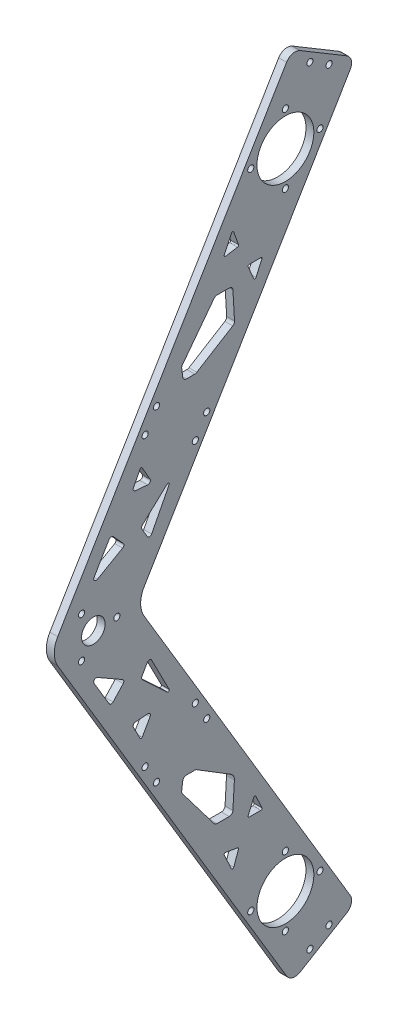
SolidWorks part; units mm, degrees
ref_plane "Front Plane" through (0, 0, 0) normal (1, 0, 0) x (0, 1, 0)
ref_plane "Top Plane" through (0, 0, 0) normal (0, 0, 1) x (0, 1, 0)
ref_plane "Right Plane" through (0, 0, 0) normal (0, 1, 0) x (-1, 0, 0)
sketch "sketch" plane through (0, 0, 0) normal (1, 0, 0) x (0, 1, 0)
  line L0 (260, 0) -> (-260, 0) construction
  line L1 (0, 0) -> (0, 280) construction
  line L2 (0, 280) -> (0, 197.29) construction
  line L3 (0, 197.29) -> (260, 0) construction
  line L4 (0, 197.29) -> (-260, 0) construction
  line L5 (0, 0) -> (130, 98.645) construction
  line L6 (130, 98.645) -> (130, 119.61) construction
  line L7 (130, 98.645) -> (130, 77.68) construction
  line L8 (130, 77.68) -> (0, 0) construction
  line L9 (130, 77.68) -> (260, 0) construction
  circle A0 centre (0, 0) radius 65 construction
  circle A1 centre (260, 0) radius 65 construction
  circle A2 centre (-260, 0) radius 65 construction
  point P4 (0, 0)
  dimension "D1" = 130
  dimension "D2" = 130
  dimension "D4" = 130
  dimension "D5" = 280
  dimension "D3" = 260
  dimension "D6" = 82.71
  dimension "D7" = 20.965
  dimension "D8" = 20.965
sketch "bogie base" plane through (0, 0, 0) normal (1, 0, 0) x (0, 1, 0)
  line L1 (260, 0) -> (-260, 0) construction
  line L3 (-25.7527, -15.3882) -> (9.8719, 5.8988) construction
  line L9 (-31.3951, -5.9456) -> (-20.1104, -24.8309)
  line L15 (285.7527, -15.3882) -> (234.2473, 15.3882) construction
  line L16 (130, 77.68) -> (260, 0) construction
  line L17 (291.3951, -5.9456) -> (280.1104, -24.8309)
  line L25 (124.8706, 92.0889) -> (-30.0131, -0.4601)
  line L26 (124.8706, 57.1411) -> (-14.6249, -26.2128)
  line L27 (135.1294, 57.1411) -> (274.6249, -26.2128)
  line L28 (135.1294, 92.0889) -> (290.0131, -0.4601)
  circle A0 centre (260, 0) radius 11.5 construction
  circle A1 centre (0, 0) radius 11.5 construction
  arc A2 (124.8706, 57.1411) -> (135.1294, 57.1411) centre (130, 48.5569) cw
  arc A3 (124.8706, 92.0889) -> (135.1294, 92.0889) centre (130, 83.5046) cw
  arc A4 (291.3951, -5.9456) -> (290.0131, -0.4601) centre (287.9614, -3.8938) ccw
  arc A5 (280.1104, -24.8309) -> (274.6249, -26.2128) centre (276.6767, -22.7791) cw
  arc A6 (-14.6249, -26.2128) -> (-20.1104, -24.8309) centre (-16.6767, -22.7791) cw
  arc A7 (-31.3951, -5.9456) -> (-30.0131, -0.4601) centre (-27.9614, -3.8938) cw
  point P4 (130, 98.645)
  point P12 (0, 0)
  point P14 (-25.7527, -15.3882)
  point P18 (260, 0)
  point P19 (0, 0)
  point P24 (130, 98.645)
  point P26 (260, 0)
  point P29 (285.7527, -15.3882)
  point P33 (130, 60.2061)
  point P35 (130, 77.68)
  point P37 (130, 95.1539)
  point P38 (130, 77.68)
  point P41 (130, 98.645)
  point P43 (293.4468, -2.5119)
  point P46 (278.0586, -28.2646)
  point P49 (-18.0586, -28.2646)
  point P52 (-33.4468, -2.5119)
  dimension "D11" = 23
  dimension "D12" = 118.28
  dimension "D2" = 23
  dimension "D14" = 10
  dimension "D15" = 10
  dimension "D16" = 4
  dimension "D3" = 90
  dimension "D4" = 30
  dimension "D5" = 30
  dimension "D6" = 90
  dimension "D7" = 30
  dimension "D8" = 30
  dimension "D9" = 190.4034
  dimension "D10" = 34.9478
  dimension "D13" = 241.72
extrude "extrude-base" add sketch "bogie base" along normal blind 3.18
sketch "Sketch4" plane through (0, 0, 0) normal (1, 0, 0) x (0, 1, 0)
  circle A0 centre (260, 0) radius 11.5
  circle A1 centre (0, 0) radius 11.5
  dimension "D1" = 23
  dimension "D2" = 23
extrude "Cut-motor holes\\" cut sketch "Sketch4" along normal blind 3.18
sketch "Sketch5" plane through (0, 0, 0) normal (1, 0, 0) x (0, 1, 0)
  line L0 (0, 15.25) -> (0, -15.25) construction
  line L4 (24.7016, 0) -> (-24.7016, 0) construction
  line L5 (0, 11.5) -> (0, 14) construction
  line L6 (8.1317, 8.1317) -> (-8.1317, -8.1317) construction
  line L8 (251.8683, 8.1317) -> (268.1317, -8.1317) construction
  line L9 (260, 11.5) -> (260, 14) construction
  line L10 (235.2984, 0) -> (284.7016, 0) construction
  circle A0 centre (0, 0) radius 11.5 construction
  circle A1 centre (0, 14) radius 1.25
  circle A2 centre (0, -14) radius 1.25
  circle A3 centre (14, 0) radius 1.25
  circle A4 centre (-14, 0) radius 1.25
  circle A5 centre (260, 0) radius 11.5 construction
  circle A6 centre (274, 0) radius 1.25
  circle A7 centre (246, 0) radius 1.25
  circle A8 centre (260, -14) radius 1.25
  circle A9 centre (260, 14) radius 1.25
  point P13 (0, 0)
  point P22 (0, 0)
  point P45 (260, 0)
  point P46 (260, 0)
  dimension "D1" = 2.5
  dimension "D2" = 14
extrude "motor support holes" cut sketch "Sketch5" along normal blind 3.18
sketch "Sketch6" plane through (0, 0, 0) normal (1, 0, 0) x (0, 1, 0)
  line L0 (130, 82.445) -> (130, 66.92) construction
  line L2 (-25.7527, -15.3882) -> (-23.0229, -13.7571) construction
  line L3 (-25.7527, -15.3882) -> (9.8719, 5.8988) construction
  line L5 (-30.717, -0.8807) -> (-15.3288, -26.6334) construction
  line L6 (124.8706, 57.1411) -> (-14.6249, -26.2128) construction
  line L7 (-25.3312, -9.8942) -> (-20.7147, -17.62) construction
  line L9 (-31.3951, -5.9456) -> (-20.1104, -24.8309) construction
  line L10 (106.8543, 81.3234) -> (122.2425, 55.5707) construction
  line L12 (-23.0229, -13.7571) -> (18.1814, 10.8641) construction
  line L13 (130, 77.68) -> (0, 0) construction
  line L14 (130, 77.68) -> (18.1814, 10.8641) construction
  line L15 (66.3966, 57.1484) -> (81.7848, 31.3957) construction
  line L16 (10.4873, 23.7405) -> (25.8755, -2.0123) construction
  line L17 (77.9536, 46.5803) -> (70.2278, 41.9638) construction
  line L18 (62.5337, 54.8402) -> (77.9219, 29.0875) construction
  line L19 (70.2595, 59.4566) -> (85.6477, 33.7039) construction
  line L20 (62.5337, 54.8402) -> (64.1648, 52.1104) construction
  line L21 (130, 77.68) -> (130, 68.17) construction
  line L22 (130, 68.17) -> (121.7723, 82.4492) construction
  line L23 (121.7723, 82.4492) -> (138.2488, 82.437) construction
  line L24 (138.2488, 82.437) -> (130, 68.17) construction
  line L25 (130, 77.68) -> (121.7723, 82.4492) construction
  circle A17 centre (-25.3312, -9.8942) radius 1.25
  circle A18 centre (-20.7147, -17.62) radius 1.25
  circle A19 centre (64.1648, 52.1104) radius 1.25
  circle A20 centre (71.8906, 56.7269) radius 1.25
  circle A21 centre (76.2908, 31.8172) radius 1.25
  circle A22 centre (84.0166, 36.4337) radius 1.25
  circle A23 centre (130, 77.68) radius 4.765
  circle A24 centre (130, 68.17) radius 1.25
  circle A25 centre (121.7723, 82.4492) radius 1.25
  circle A26 centre (138.2488, 82.437) radius 1.25
  circle A27 centre (175.9834, 36.4337) radius 1.25
  circle A28 centre (183.7092, 31.8172) radius 1.25
  circle A29 centre (195.8352, 52.1104) radius 1.25
  circle A30 centre (188.1094, 56.7269) radius 1.25
  circle A31 centre (280.7147, -17.62) radius 1.25
  circle A32 centre (285.3312, -9.8942) radius 1.25
  point P12 (-23.0229, -13.7571)
  point P15 (-23.0229, -13.7571)
  point P25 (114.5484, 68.4471)
  point P32 (74.0907, 44.272)
  point P35 (18.1814, 10.8641)
  point P38 (74.0907, 44.272)
  point P41 (70.2278, 41.9638)
  point P44 (77.9536, 46.5803)
  dimension "D4" = 2.5
  dimension "D5" = 18
  dimension "D8" = 48
  dimension "D9" = 30
  dimension "D10" = 4.5
  dimension "D1" = 3.18
  dimension "D2" = 2.5
  dimension "D3" = 9
  dimension "D11" = 2.5
  dimension "D13" = 9.53
  dimension "D14" = 2.5
  dimension "D20" = 2.5
  dimension "D21" = 2.5
  dimension "D22" = 19.6131
  dimension "D6" = 30
  dimension "D7" = 30.86
  dimension "D12" = 3.18
  dimension "D15" = 9.51
  dimension "D16" = 16.48
  dimension "D17" = 16.4764
  dimension "D18" = 16.48
  dimension "D19" = 9.51
extrude "support holes" cut sketch "Sketch6" along normal blind 3.18
sketch "Sketch7" plane through (0, 0, 0) normal (1, 0, 0) x (0, 1, 0)
  line L0 (111.4204, 77.3885) -> (101.2093, 71.287)
  line L1 (101.0405, 69.697) -> (105.4282, 65.6076)
  line L2 (106.9782, 65.843) -> (112.8016, 76.034)
  line L3 (107.9696, 55.8657) -> (104.1511, 58.0477)
  line L4 (102.9234, 57.8613) -> (93.556, 47.8105)
  line L5 (94.1503, 47.0249) -> (107.9306, 54.1081)
  line L6 (88.0497, 61.4547) -> (82.8599, 58.7871)
  line L7 (82.8404, 57.9083) -> (88.3944, 54.7346)
  line L8 (130, 77.68) -> (0, 0) construction
  line L9 (89.8876, 55.6799) -> (89.5039, 60.6424)
  line L10 (54.884, 41.6464) -> (38.0344, 28.8608)
  line L11 (0, 0) -> (130, 98.645) construction
  line L12 (37.4411, 27.6659) -> (37.4411, 22.7346)
  line L13 (38.8533, 21.2372) -> (49.1659, 20.6321)
  line L14 (51.8962, 22.054) -> (60.3984, 35.8618)
  line L15 (60.6211, 36.6482) -> (60.6211, 40.0362)
  line L16 (59.3068, 41.5246) -> (55.9763, 41.9399)
  line L17 (24.8845, 24.7214) -> (18.7051, 21.8314)
  line L18 (18.7465, 20.9084) -> (24.1386, 18.9527)
  line L19 (24.8026, 19.3426) -> (25.5899, 24.1883)
  line L20 (39.1024, 11.9231) -> (33.9164, 9.4977)
  line L21 (33.2046, 9.9506) -> (33.2046, 14.5862)
  line L22 (33.9006, 15.0462) -> (39.0866, 12.836)
  line L23 (130, 93.5046) -> (130, 58.5569) construction
  line L24 (226.0994, 15.0462) -> (220.9134, 12.836)
  line L25 (226.7954, 9.9506) -> (226.7954, 14.5862)
  line L26 (220.8976, 11.9231) -> (226.0836, 9.4977)
  line L27 (235.1974, 19.3426) -> (234.4101, 24.1883)
  line L28 (241.2535, 20.9084) -> (235.8614, 18.9527)
  line L29 (235.1155, 24.7214) -> (241.2949, 21.8314)
  line L30 (200.6932, 41.5246) -> (204.0237, 41.9399)
  line L31 (199.3789, 36.6482) -> (199.3789, 40.0362)
  line L32 (208.5739, 21.2905) -> (199.6016, 35.8618)
  line L33 (221.1467, 21.2372) -> (209.939, 20.5796)
  line L34 (222.5589, 27.6659) -> (222.5589, 22.7346)
  line L35 (205.116, 41.6464) -> (221.9656, 28.8608)
  line L36 (170.1124, 55.6799) -> (170.4961, 60.6424)
  line L37 (177.1596, 57.9083) -> (171.6056, 54.7346)
  line L38 (171.9503, 61.4547) -> (177.1401, 58.7871)
  line L39 (165.8497, 47.0249) -> (152.0694, 54.1081)
  line L40 (157.0766, 57.8613) -> (166.444, 47.8105)
  line L41 (152.0304, 55.8657) -> (155.8489, 58.0477)
  line L42 (153.0218, 65.843) -> (147.1984, 76.034)
  line L43 (158.9595, 69.697) -> (154.5718, 65.6076)
  line L44 (148.5796, 77.3885) -> (158.7907, 71.287)
  arc A0 (88.3944, 54.7346) -> (89.8876, 55.6799) centre (88.8906, 55.6028) ccw
  arc A1 (88.0497, 61.4547) -> (89.5039, 60.6424) centre (88.5069, 60.5654) cw
  arc A2 (104.1511, 58.0477) -> (102.9234, 57.8613) centre (103.6549, 57.1795) ccw
  arc A3 (107.9696, 55.8657) -> (107.9306, 54.1081) centre (107.4734, 54.9975) cw
  arc A4 (105.4282, 65.6076) -> (106.9782, 65.843) centre (106.11, 66.3392) ccw
  arc A5 (101.2093, 71.287) -> (101.0405, 69.697) centre (101.7223, 70.4286) ccw
  arc A6 (111.4204, 77.3885) -> (112.8016, 76.034) centre (111.9334, 76.5301) cw
  arc A7 (82.8599, 58.7871) -> (82.8404, 57.9083) centre (83.0885, 58.3424) ccw
  arc A8 (93.556, 47.8105) -> (94.1503, 47.0249) centre (93.9217, 47.4696) ccw
  arc A9 (37.4411, 22.7346) -> (38.8533, 21.2372) centre (38.9411, 22.7346) ccw
  arc A10 (38.0344, 28.8608) -> (37.4411, 27.6659) centre (38.9411, 27.6659) ccw
  arc A12 (60.3984, 35.8618) -> (60.6211, 36.6482) centre (59.1211, 36.6482) ccw
  arc A13 (60.6211, 40.0362) -> (59.3068, 41.5246) centre (59.1211, 40.0362) ccw
  arc A14 (55.9763, 41.9399) -> (54.884, 41.6464) centre (55.7907, 40.4515) ccw
  arc A15 (18.7051, 21.8314) -> (18.7465, 20.9084) centre (18.917, 21.3785) ccw
  arc A16 (24.1386, 18.9527) -> (24.8026, 19.3426) centre (24.3091, 19.4228) ccw
  arc A17 (24.8845, 24.7214) -> (25.5899, 24.1883) centre (25.0963, 24.2685) cw
  arc A18 (33.9164, 9.4977) -> (33.2046, 9.9506) centre (33.7046, 9.9506) cw
  arc A19 (33.2046, 14.5862) -> (33.9006, 15.0462) centre (33.7046, 14.5862) cw
  arc A20 (39.1024, 11.9231) -> (39.0866, 12.836) centre (38.8906, 12.376) ccw
  arc A21 (135.1294, 92.0889) -> (124.8706, 92.0889) centre (130, 83.5046) ccw construction
  arc A22 (135.1294, 57.1411) -> (124.8706, 57.1411) centre (130, 48.5569) ccw construction
  arc A23 (220.8976, 11.9231) -> (220.9134, 12.836) centre (221.1094, 12.376) cw
  arc A24 (226.7954, 14.5862) -> (226.0994, 15.0462) centre (226.2954, 14.5862) ccw
  arc A25 (226.0836, 9.4977) -> (226.7954, 9.9506) centre (226.2954, 9.9506) ccw
  arc A26 (235.1155, 24.7214) -> (234.4101, 24.1883) centre (234.9037, 24.2685) ccw
  arc A27 (235.8614, 18.9527) -> (235.1974, 19.3426) centre (235.6909, 19.4228) cw
  arc A28 (241.2949, 21.8314) -> (241.2535, 20.9084) centre (241.083, 21.3785) cw
  arc A29 (204.0237, 41.9399) -> (205.116, 41.6464) centre (204.2093, 40.4515) cw
  arc A30 (199.3789, 40.0362) -> (200.6932, 41.5246) centre (200.8789, 40.0362) cw
  arc A31 (199.6016, 35.8618) -> (199.3789, 36.6482) centre (200.8789, 36.6482) cw
  arc A32 (209.939, 20.5796) -> (208.5739, 21.2905) centre (209.8512, 22.077) cw
  arc A33 (221.9656, 28.8608) -> (222.5589, 27.6659) centre (221.0589, 27.6659) cw
  arc A34 (222.5589, 22.7346) -> (221.1467, 21.2372) centre (221.0589, 22.7346) cw
  arc A35 (166.444, 47.8105) -> (165.8497, 47.0249) centre (166.0783, 47.4696) cw
  arc A36 (177.1401, 58.7871) -> (177.1596, 57.9083) centre (176.9115, 58.3424) cw
  arc A37 (148.5796, 77.3885) -> (147.1984, 76.034) centre (148.0666, 76.5301) ccw
  arc A38 (158.7907, 71.287) -> (158.9595, 69.697) centre (158.2777, 70.4286) cw
  arc A39 (154.5718, 65.6076) -> (153.0218, 65.843) centre (153.89, 66.3392) cw
  arc A40 (152.0304, 55.8657) -> (152.0694, 54.1081) centre (152.5266, 54.9975) ccw
  arc A41 (155.8489, 58.0477) -> (157.0766, 57.8613) centre (156.3451, 57.1795) cw
  arc A42 (171.9503, 61.4547) -> (170.4961, 60.6424) centre (171.4931, 60.5654) ccw
  arc A43 (171.6056, 54.7346) -> (170.1124, 55.6799) centre (171.1094, 55.6028) cw
  arc A44 (51.8962, 22.054) -> (49.1659, 20.6321) centre (49.3417, 23.6269) cw
  point P27 (90.0331, 53.7982)
  point P48 (37.4411, 28.4106)
  point P53 (60.6211, 36.2235)
  point P58 (55.3704, 42.0155)
  point P63 (24.7059, 18.747)
  point P143 (235.2941, 18.747)
  point P144 (204.6296, 42.0155)
  point P145 (199.3789, 36.2235)
  point P146 (222.5589, 28.4106)
  point P147 (169.9669, 53.7982)
  dimension "D1" = 1
  dimension "D2" = 0.5
  dimension "D3" = 1.5
  dimension "D4" = 0.5
  dimension "D5" = 3
extrude "Cut-lightening holes" cut sketch "Sketch7" along normal blind 3.18
